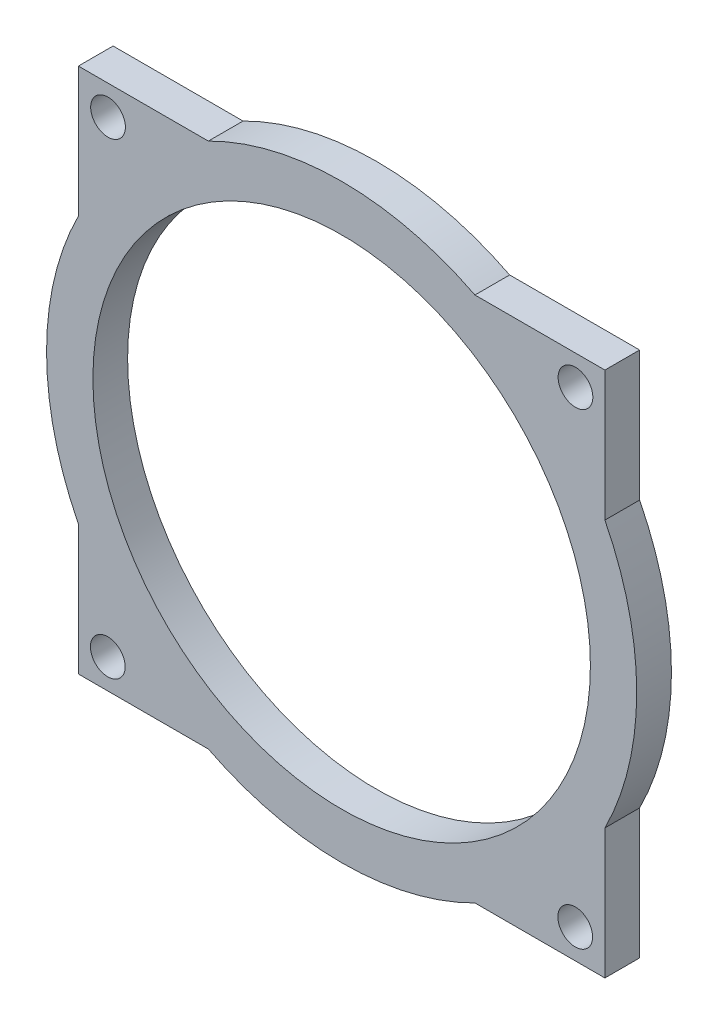
SolidWorks part; units mm, degrees
ref_plane "Front Plane" through (0, 0, 0) normal (0, 0, 1) x (1, 0, 0)
ref_plane "Top Plane" through (0, 0, 0) normal (0, 1, 0) x (1, 0, 0)
ref_plane "Right Plane" through (0, 0, 0) normal (1, 0, 0) x (0, 0, -1)
sketch "Sketch1" plane through (0, 0, 0) normal (0, 0, 1) x (1, 0, 0)
  line L0 (22.75, -22.75) -> (22.75, -11.519)
  line L1 (22.75, -12.5872) -> (22.75, 12.5872) construction
  line L2 (22.75, -22.75) -> (11.519, -22.75)
  line L3 (-22.75, -22.75) -> (-11.519, -22.75)
  line L4 (-12.5872, -22.75) -> (12.5872, -22.75) construction
  line L5 (-22.75, -22.75) -> (-22.75, -11.519)
  line L6 (-22.75, 12.5872) -> (-22.75, -12.5872) construction
  line L7 (-22.75, 22.75) -> (-22.75, 11.519)
  line L8 (-22.75, 22.75) -> (-11.519, 22.75)
  line L9 (22.75, 22.75) -> (11.519, 22.75)
  line L10 (22.75, 22.75) -> (22.75, 11.519)
  arc A0 (-22.75, 11.519) -> (11.519, -22.75) centre (0, 0) ccw
  arc A1 (11.519, 22.75) -> (-11.519, 22.75) centre (0, 0) ccw
  circle A2 centre (20.1888, -20.2074) radius 1.5
  circle A3 centre (-20.2074, -20.1888) radius 1.5
  circle A8 centre (0, 0) radius 21.4962
  circle A9 centre (0, 0) radius 25.5 construction
  arc A10 (22.75, -11.519) -> (22.75, 11.519) centre (0, 0) ccw
  circle A11 centre (-20.1888, 20.2074) radius 1.5
  circle A12 centre (20.2074, 20.1888) radius 1.5
  point P11 (0, 0)
  dimension "D1" = 3
  dimension "D2" = 4
extrude "Boss-Extrude1" add sketch "Sketch1" along normal blind 3 contours L0 A10 L10 L9 A1 L8 L7 A0 L2 A12 A11 A2 A8 | A0 L5 L3 A3 region at (17.1345, -22.0288, 0) region at (-17.1345, -22.5912, 0)
